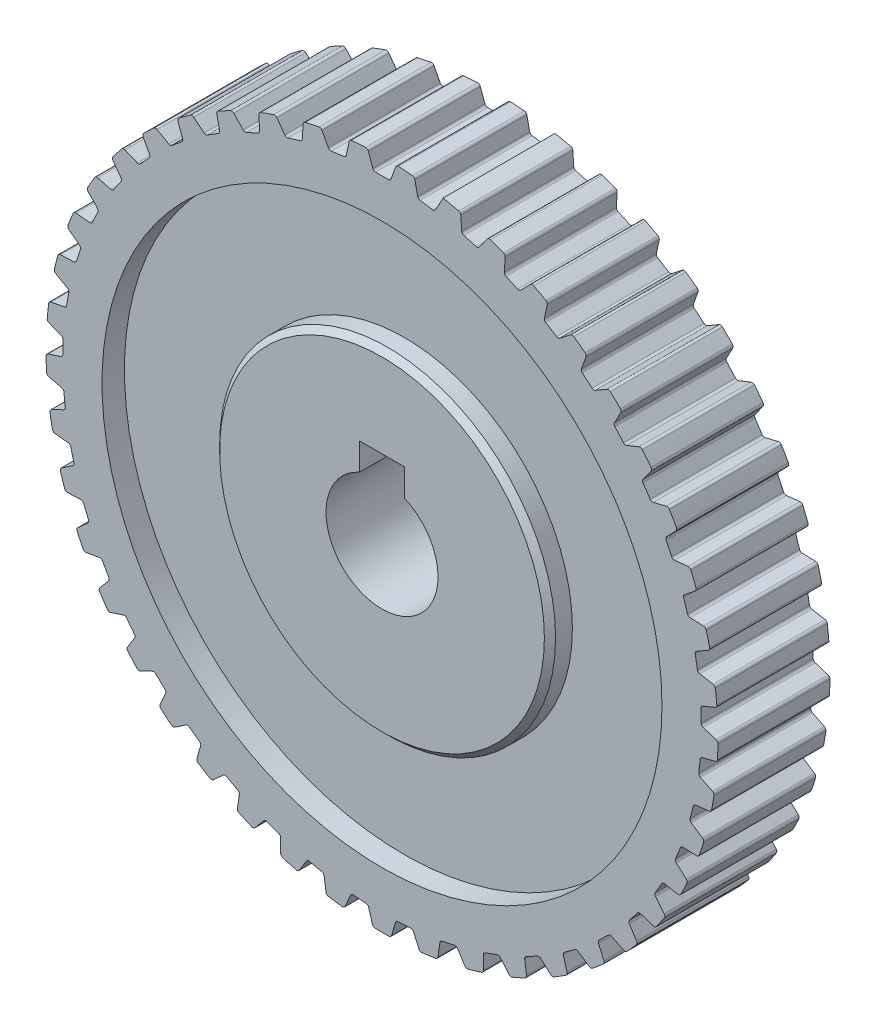
SolidWorks part; units mm, degrees
ref_plane "Front Plane" through (0, 0, 0) normal (0, 0, 1) x (1, 0, 0)
ref_plane "Top Plane" through (0, 0, 0) normal (0, 1, 0) x (1, 0, 0)
ref_plane "Right Plane" through (0, 0, 0) normal (1, 0, 0) x (0, 0, -1)
sketch "Sketch1" plane through (0, 0, 0) normal (0, 0, 1) x (1, 0, 0)
  line L0 (0, 0) -> (0, 18.0845) construction
  line L2 (-2, 7) -> (2, 7)
  line L3 (-2, 7) -> (-2, 4.5826)
  line L5 (2, 7) -> (2, 4.5826)
  circle A0 centre (0, 0) radius 30
  arc A1 (-2, 4.5826) -> (2, 4.5826) centre (0, 0) ccw
  dimension "D1" = 60
  dimension "D2" = 10
  dimension "D3" = 4
  dimension "D4" = 7
extrude "Boss-Extrude1" add sketch "Sketch1" along normal mid plane 10
sketch "Sketch2" plane through (0, 0, 5) normal (0, 0, 1) x (1, 0, 0)
  line L0 (0, 0) -> (0, 30) construction
  line L1 (-1.2859, 29.9724) -> (-0.75, 28.5)
  line L2 (-0.75, 28.5) -> (0.75, 28.5)
  line L3 (0.75, 28.5) -> (1.2859, 29.9724)
  circle A0 centre (0, 0) radius 30 construction
  circle M5 centre (0, 0) radius 30
  dimension "D1" = 1.5
  dimension "D2" = 20
  dimension "D3" = 28.5
extrude "Cut-Extrude1" cut sketch "Sketch2" against normal blind 10 and the other way through all contours L2 L0 L1 M5 | L0 L2 L3 M5 region at (-0.5201, 29.3114, 5) region at (0.5201, 29.3114, 5)
pattern_circular "CirPattern1" count 45 over 360 about axis through (0, 0, 5) along (0, 0, 1) of "Cut-Extrude1"
sketch "Sketch3" plane through (0, 0, 5) normal (0, 0, 1) x (1, 0, 0)
  circle A0 centre (0, 0) radius 25
  dimension "D1" = 50
extrude "Cut-Extrude-Thin1" cut sketch "Sketch3" against normal blind 2 thin thin type one direction reverse wall 10
mirror "Mirror1" about plane through (0, 0, 0) normal (0, 0, 1) of "Cut-Extrude-Thin1"
chamfer "Chamfer1" distance 0.5 angle 45 2 edges at (15, 0, -5) (15, 0, 5)
fillet "Fillet1" radius 0.25 179 edges at (28.2655, -3.725, 0) (28.4223, -2.2332, 0) (29.9427, -1.8541, 0) (29.999, -0.2391, 0) (28.5088, 0.2451, 0) (28.4565, 1.7442, 0) (29.9093, 2.3312, 0) (29.7404, 3.9383, 0) (28.1973, 4.2104, 0) (27.9368, 5.6876, 0) (29.2938, 6.471, 0) (28.9028, 8.039, 0) (27.3369, 8.0937, 0) (26.8733, 9.5203, 0) (28.1081, 10.485, 0) (27.5027, 11.9833, 0) (25.9444, 11.8195, 0) (25.2869, 13.1677, 0) (26.3753, 14.2948, 0) (25.5673, 15.6943, 0) (24.047, 15.3152, 0) (23.2082, 16.5588, 0) (24.1292, 17.8264, 0) (23.1343, 19.0998, 0) (21.6815, 18.5129, 0) (20.6778, 19.6276, 0) (21.4134, 21.0111, 0) (20.251, 22.1336, 0) (18.894, 21.3502, 0) (17.7449, 22.3144, 0) (18.2808, 23.7868, 0) (16.9735, 24.7366, 0) (15.7387, 23.7719, 0) (14.4667, 24.5668, 0) (14.7924, 26.0995, 0) (13.3656, 26.8581, 0) (12.2772, 25.731, 0) (10.9068, 26.3411, 0) (11.0161, 27.9042, 0) (9.4976, 28.4569, 0) (8.5766, 27.1892, 0) (7.1347, 27.6027, 0) (4.7091, 28.1183, 0) (3.2237, 28.327, 0) (2.898, 29.8597, 0) (0.75, 28.5, 0) (-0.75, 28.5, 0) (-2.898, 29.8597, 0) (-3.2237, 28.327, 0) (-4.7091, 28.1183, 0) (-5.4448, 29.5018, 0) (-7.0254, 29.1658, 0) (-7.1347, 27.6027, 0) (-8.5766, 27.1892, 0) (-9.4976, 28.4569, 0) (-11.0161, 27.9042, 0) (-10.9068, 26.3411, 0) (-12.2772, 25.731, 0) (-13.3656, 26.8581, 0) (-14.7924, 26.0995, 0) (-14.4667, 24.5668, 0) (-15.7387, 23.7719, 0) (-16.9735, 24.7366, 0) (-18.2808, 23.7868, 0) (-17.7449, 22.3144, 0) (-18.894, 21.3502, 0) (-20.251, 22.1336, 0) (-21.4134, 21.0111, 0) (-20.6778, 19.6276, 0) (-21.6815, 18.5129, 0) (-23.1343, 19.0998, 0) (-24.1292, 17.8264, 0) (-23.2082, 16.5588, 0) (-24.047, 15.3152, 0) (-25.5673, 15.6943, 0) (-26.3753, 14.2948, 0) (-25.2869, 13.1677, 0) (-25.9444, 11.8195, 0) (-27.5027, 11.9833, 0) (-28.1081, 10.485, 0) (-26.8733, 9.5203, 0) (-27.3369, 8.0937, 0) (-28.9028, 8.039, 0) (-29.2938, 6.471, 0) (-27.9368, 5.6876, 0) (-28.1973, 4.2104, 0) (-29.7404, 3.9383, 0) (-29.9093, 2.3312, 0) (-28.4565, 1.7442, 0) (-28.5088, 0.2451, 0) (-29.999, -0.2391, 0) (-29.9427, -1.8541, 0) (-28.4223, -2.2332, 0) (-28.2655, -3.725, 0) (-29.6738, -4.4118, 0) (-29.3932, -6.0033, 0) (-27.8349, -6.1671, 0) (-27.472, -7.6225, 0) (-28.771, -8.4987, 0) (-28.2717, -10.0356, 0) (-26.7057, -9.9809, 0) (-26.1438, -11.3717, 0) (-27.3082, -12.4202, 0) (-26.5998, -13.8726, 0) (-25.0567, -13.6005, 0) (-24.3067, -14.8995, 0) (-25.3139, -16.0999, 0) (-24.4103, -17.4396, 0) (-22.9201, -16.9553, 0) (-21.9966, -18.1374, 0) (-22.8269, -19.4662, 0) (-21.7456, -20.6671, 0) (-20.3373, -19.9802, 0) (-19.2583, -21.0222, 0) (-19.8956, -22.4536, 0) (-18.6577, -23.4924, 0) (-17.3586, -22.6161, 0) (-16.1451, -23.4978, 0) (-16.577, -25.004, 0) (-15.2066, -25.8604, 0) (-14.0422, -24.8119, 0) (-12.7177, -25.5161, 0) (-12.9358, -27.0678, 0) (-11.4595, -27.7251, 0) (-10.4523, -26.5247, 0) (-9.0428, -27.0378, 0) (-9.0428, -28.6047, 0) (-7.4894, -29.0501, 0) (-6.6591, -27.7213, 0) (-5.1919, -28.0331, 0) (-4.9738, -29.5848, 0) (-3.3736, -29.8097, 0) (-2.7362, -28.3783, 0) (-1.2399, -28.4829, 0) (-0.808, -29.9891, 0) (0.808, -29.9891, 0) (1.2399, -28.4829, 0) (2.7362, -28.3783, 0) (3.3736, -29.8097, 0) (4.9738, -29.5848, 0) (5.1919, -28.0331, 0) (6.6591, -27.7213, 0) (7.4894, -29.0501, 0) (9.0428, -28.6047, 0) (9.0428, -27.0378, 0) (10.4523, -26.5247, 0) (11.4595, -27.7251, 0) (12.9358, -27.0678, 0) (12.7177, -25.5161, 0) (14.0422, -24.8119, 0) (15.2066, -25.8604, 0) (16.577, -25.004, 0) (16.1451, -23.4978, 0) (17.3586, -22.6161, 0) (18.6577, -23.4924, 0) (19.8956, -22.4536, 0) (19.2583, -21.0222, 0) (20.3373, -19.9802, 0) (21.7456, -20.6671, 0) (22.8269, -19.4662, 0) (21.9966, -18.1374, 0) (22.9201, -16.9553, 0) (24.4103, -17.4396, 0) (25.3139, -16.0999, 0) (24.3067, -14.8995, 0) (25.0567, -13.6005, 0) (26.5998, -13.8726, 0) (27.3082, -12.4202, 0) (26.1438, -11.3717, 0) (26.7057, -9.9809, 0) (28.2717, -10.0356, 0) (28.771, -8.4987, 0) (27.472, -7.6225, 0) (27.8349, -6.1671, 0) (29.3932, -6.0033, 0) (29.6738, -4.4118, 0) (7.0254, 29.1658, 0)
